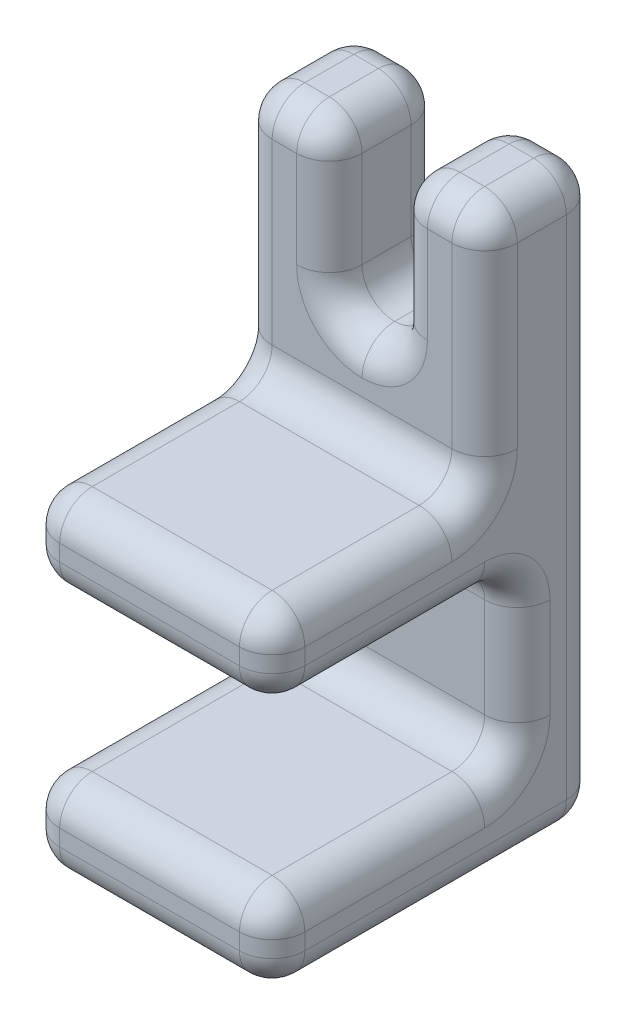
SolidWorks part; units mm, degrees
ref_plane "Front Plane" through (0, 0, 0) normal (0, 0, 1) x (1, 0, 0)
ref_plane "Top Plane" through (0, 0, 0) normal (0, 1, 0) x (1, 0, 0)
ref_plane "Right Plane" through (0, 0, 0) normal (1, 0, 0) x (0, 0, -1)
sketch "Sketch1" plane through (0, 0, 0) normal (0, 0, 1) x (1, 0, 0)
  line L1 (0, 0) -> (-15, 0)
  line L2 (0, 0) -> (0, 35)
  line L3 (0, 35) -> (-15, 35)
  line L4 (-15, 0) -> (-15, 35)
  dimension "D1" = 35
  dimension "D2" = 15
extrude "Boss-Extrude1" add sketch "Sketch1" along normal blind 20
sketch "Sketch2" plane through (0, 0, 0) normal (1, 0, 0) x (0, 0, -1)
  line L0 (-20, 0) -> (-20, 35) construction
  line L1 (-20, 15.1) -> (-5, 15.1)
  line L2 (-20, 15.1) -> (-20, 5)
  line L3 (-20, 5) -> (-5, 5)
  line L4 (-5, 15.1) -> (-5, 5)
  line L5 (-20, 0) -> (0, 0) construction
  line L6 (0, 0) -> (0, 35) construction
  dimension "D1" = 5
  dimension "D2" = 5
  dimension "10,5" = 10.1
extrude "Cut-Extrude1" cut sketch "Sketch2" against normal through all
fillet "Fillet1" radius 2 8 edges at (-15, 5, 12.5) (0, 5, 12.5) (-15, 15.1, 12.5) (0, 15.1, 12.5) (-7.5, 5, 5) (-15, 10.05, 5) (-7.5, 15.1, 5) (0, 10.05, 5)
sketch "Sketch4" plane through (-15, 0, 0) normal (-1, 0, 0) x (0, 0, 1)
  line L1 (20, 20.1) -> (7, 20.1)
  line L2 (20, 20.1) -> (20, 35)
  line L3 (20, 35) -> (7, 35)
  line L4 (7, 20.1) -> (7, 35)
  line L12 (20, 15.1) -> (7, 15.1) construction
  dimension "D1" = 5
extrude "Cut-Extrude3" cut sketch "Sketch4" against normal through all
sketch "Sketch5" plane through (0, 0, 0) normal (0, 0, -1) x (-1, 0, 0)
  line L1 (5.5, 35) -> (9.5, 35)
  line L2 (5.5, 35) -> (5.5, 25.1)
  line L3 (5.5, 25.1) -> (9.5, 25.1)
  line L4 (9.5, 35) -> (9.5, 25.1)
  line L6 (5.5, 25.1) -> (9.5, 25.1) construction
  line L9 (0, 35) -> (15, 35) construction
  line L10 (0, 35) -> (15, 35) construction
  line L11 (0, 20.1) -> (15, 20.1) construction
  point P10 (7.5, 35)
  point P11 (7.5, 35)
  dimension "D1" = 4
  dimension "D2" = 5
extrude "Cut-Extrude4" cut sketch "Sketch5" against normal up to next and the other way through all
fillet "Fillet2" radius 2 38 edges at (-9.5, 35, 3.5) (-5.5, 35, 3.5) (-5.5, 25.1, 3.5) (-9.5, 25.1, 3.5) (-2.75, 35, 7) (-12.25, 35, 7) (-9.5, 30.05, 7) (-7.5, 25.1, 7) (-5.5, 30.05, 7) (-7.5, 20.1, 7) (-15, 35, 3.5) (-15, 27.55, 7) (-15, 20.1, 13.5) (-0.5858, 4.4142, 20) (-15, 1.5, 20) (-14.4142, 4.4142, 20) (-7.5, 5, 20) (-0.5858, 15.6858, 20) (-7.5, 15.1, 20) (-14.4142, 15.6858, 20) (-15, 18.6, 20) (-7.5, 20.1, 20) (0, 35, 3.5) (0, 1.5, 20) (0, 18.6, 20) (0, 20.1, 13.5) (0, 27.55, 7) (-15, 0, 10) (-7.5, 0, 20) (0, 0, 10) (-7.5, 25.1, 0) (-9.5, 30.05, 0) (-12.25, 35, 0) (-15, 17.5, 0) (-7.5, 0, 0) (0, 17.5, 0) (-2.75, 35, 0) (-5.5, 30.05, 0)
